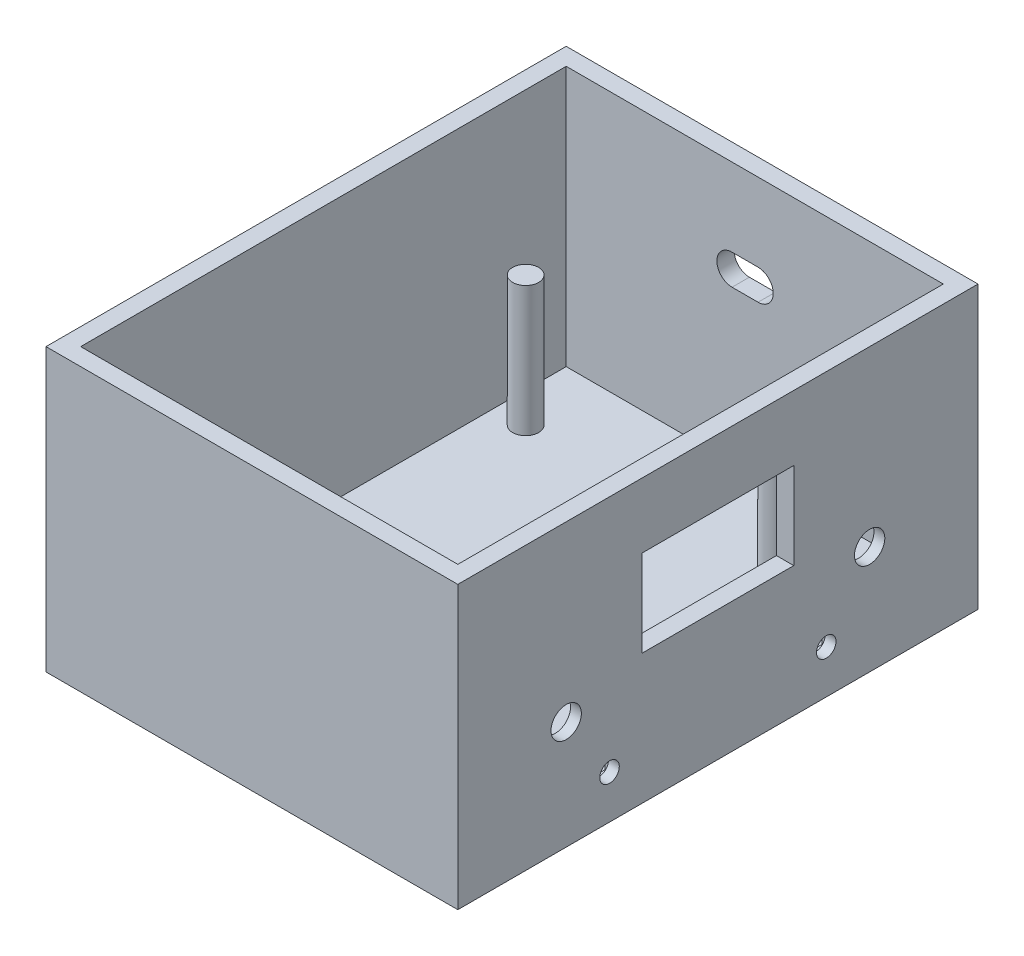
SolidWorks part; units mm, degrees
ref_plane "Front Plane" through (0, 0, 0) normal (0, 0, 1) x (1, 0, 0)
ref_plane "Top Plane" through (0, 0, 0) normal (0, 1, 0) x (1, 0, 0)
ref_plane "Right Plane" through (0, 0, 0) normal (1, 0, 0) x (0, 0, -1)
sketch "Sketch1" plane through (0, 0, 0) normal (0, 1, 0) x (1, 0, 0)
  line L1 (-47.5, -60) -> (47.5, -60)
  line L2 (-47.5, -60) -> (-47.5, 60)
  line L3 (-47.5, 60) -> (47.5, 60)
  line L4 (47.5, -60) -> (47.5, 60)
  line L5 (-47.5, -60) -> (47.5, 60) construction
  line L6 (-47.5, 60) -> (47.5, -60) construction
  point P0 (0, 0)
  dimension "D1" = 120
  dimension "D2" = 95
extrude "base dimensions" add sketch "Sketch1" along normal blind 5
sketch "Sketch2" plane through (0, 5, 0) normal (0, 1, 0) x (1, 0, 0)
  line L0 (47.5, -60) -> (47.5, 60) construction
  line L1 (-47.5, -60) -> (47.5, -60) construction
  line L2 (-47.5, 60) -> (-47.5, -60) construction
  line L3 (47.5, 60) -> (-47.5, 60) construction
  line L4 (47.5, -60) -> (47.5, 60)
  line L5 (-47.5, -60) -> (47.5, -60)
  line L6 (-47.5, 60) -> (-47.5, -60)
  line L7 (47.5, 60) -> (-47.5, 60)
  line L9 (-43.5, -56) -> (43.5, -56)
  line L10 (-43.5, -56) -> (-43.5, 56)
  line L11 (-43.5, 56) -> (43.5, 56)
  line L12 (43.5, -56) -> (43.5, 56)
  line L13 (-43.5, -56) -> (43.5, 56) construction
  line L14 (-43.5, 56) -> (43.5, -56) construction
  point P4 (0, 0)
  dimension "D1" = 4
  dimension "D2" = 4
extrude "wall height and depth" add sketch "Sketch2" along normal blind 60
sketch "Sketch3" plane through (0, 5, 0) normal (0, 1, 0) x (1, 0, 0)
  line L0 (-43.5, 56) -> (-43.5, -56) construction
  line L1 (-43.5, -56) -> (43.5, -56) construction
  circle A0 centre (-36.5, 39.645) radius 3
  circle A1 centre (-36.5, -41) radius 3
  circle A2 centre (34.62, -41) radius 3
  circle A3 centre (21.285, 39.645) radius 3
  dimension "D4" = 6
  dimension "D1" = 57.785
  dimension "D2" = 71.12
  dimension "D3" = 80.645
  dimension "D5" = 7
  dimension "D6" = 15
extrude "support pegs" add sketch "Sketch3" along normal blind 30
sketch "Sketch4" plane through (47.5, 0, 0) normal (1, 0, 0) x (0, 0, -1)
  line L0 (0, 71.0913) -> (0, -6.0913) construction
  line L1 (-17.5, 50) -> (17.5, 50)
  line L2 (-17.5, 50) -> (-17.5, 30)
  line L3 (-17.5, 30) -> (17.5, 30)
  line L4 (17.5, 50) -> (17.5, 30)
  line L5 (-17.5, 50) -> (17.5, 30) construction
  line L6 (-17.5, 30) -> (17.5, 50) construction
  line L7 (52.25, 0) -> (-52.25, 0) construction
  line L8 (-60, 65) -> (60, 65) construction
  circle A0 centre (-35, 25) radius 3.5
  circle A1 centre (-25, 10) radius 2.25
  circle A2 centre (25, 10) radius 2.25
  circle A3 centre (35, 25) radius 3.5
  point P0 (0, 40)
  point P12 (25, 10)
  dimension "D3" = 7
  dimension "D4" = 4.5
  dimension "D1" = 25
  dimension "D2" = 35
  dimension "D5" = 10
  dimension "D6" = 25
  dimension "D7" = 20
  dimension "D8" = 35
  dimension "D9" = 25
extrude "front holes" cut sketch "Sketch4" against normal up to surface (4 mm away) up to face at (43.5, 35, 0)
sketch "Sketch6" plane through (43.5, 0, 0) normal (-1, 0, 0) x (0, 0, 1)
  line L0 (0, -35.75) -> (0, 35.75) construction
  line L1 (-41.75, 31.375) -> (-28.25, 31.375)
  line L2 (-41.75, 31.375) -> (-41.75, 18.625)
  line L3 (-41.75, 18.625) -> (-28.25, 18.625)
  line L4 (-28.25, 31.375) -> (-28.25, 18.625)
  line L5 (-41.75, 31.375) -> (-28.25, 18.625) construction
  line L6 (-41.75, 18.625) -> (-28.25, 31.375) construction
  line L7 (-28, 7) -> (-22, 7)
  line L8 (-28, 7) -> (-28, 13)
  line L9 (-28, 13) -> (-22, 13)
  line L10 (-22, 7) -> (-22, 13)
  line L11 (-28, 7) -> (-22, 13) construction
  line L12 (-28, 13) -> (-22, 7) construction
  line L13 (28, 13) -> (22, 7) construction
  line L14 (28, 7) -> (22, 13) construction
  line L15 (41.75, 18.625) -> (28.25, 31.375) construction
  line L16 (41.75, 31.375) -> (28.25, 18.625) construction
  line L17 (22, 7) -> (22, 13)
  line L18 (28, 13) -> (22, 13)
  line L19 (28, 7) -> (28, 13)
  line L20 (28, 7) -> (22, 7)
  line L21 (28.25, 31.375) -> (28.25, 18.625)
  line L22 (41.75, 18.625) -> (28.25, 18.625)
  line L23 (41.75, 31.375) -> (41.75, 18.625)
  line L24 (41.75, 31.375) -> (28.25, 31.375)
  point P0 (-35, 25)
  point P6 (-25, 10)
  point P22 (25, 10)
  point P23 (35, 25)
  dimension "D1" = 13.5
  dimension "D2" = 12.75
  dimension "D3" = 6
extrude "en and b inlay" cut sketch "Sketch6" against normal blind 1.5
sketch "screen mounting layout" plane through (43.5, 0, 0) normal (-1, 0, 0) x (0, 0, 1)
  line L0 (0, -35.75) -> (0, 35.75) construction
  line L8 (-15.265, 24.85) -> (15.265, 24.85) construction
  line L9 (-15.265, 24.85) -> (-15.265, 53.46) construction
  line L10 (-15.265, 53.46) -> (15.265, 53.46) construction
  line L11 (15.265, 24.85) -> (15.265, 53.46) construction
  line L12 (-15.265, 24.85) -> (15.265, 53.46) construction
  line L13 (-15.265, 53.46) -> (15.265, 24.85) construction
  line L14 (-15.265, 23.3) -> (15.265, 23.3) construction
  line L15 (17.5, 30) -> (-17.5, 30) construction
  circle A0 centre (-15.265, 53.46) radius 1.55 construction
  circle A1 centre (-15.265, 24.85) radius 1.55 construction
  circle A2 centre (15.265, 24.85) radius 1.55 construction
  circle A3 centre (15.265, 53.46) radius 1.55 construction
  point P8 (0, 39.155)
  dimension "D3" = 3.1
  dimension "D4" = 3.1
  dimension "D1" = 30.53
  dimension "D2" = 28.61
  dimension "D5" = 6.7
sketch "Sketch9" plane through (0, 0, -56) normal (0, 0, 1) x (1, 0, 0)
  line L0 (-5.236, 43.5) -> (0.764, 43.5) construction
  line L1 (-5.236, 47) -> (0.764, 47)
  line L2 (-5.236, 40) -> (0.764, 40)
  line L3 (43.5, 5) -> (-43.5, 5) construction
  line L4 (-43.5, 65) -> (-43.5, 5) construction
  arc A0 (-5.236, 47) -> (-5.236, 40) centre (-5.236, 43.5) ccw
  arc A1 (0.764, 40) -> (0.764, 47) centre (0.764, 43.5) ccw
  point P2 (-2.236, 43.5)
  point P7 (1.2298, 30.4317)
  point P8 (-6.5963, 32.2205)
  point P9 (4.1367, 32.5559)
  point P10 (-2.236, 34.5683)
  dimension "D2" = 3.5
  dimension "D1" = 6
  dimension "D3" = 35
  dimension "D4" = 41.264
extrude "usb slot" cut sketch "Sketch9" against normal through all
